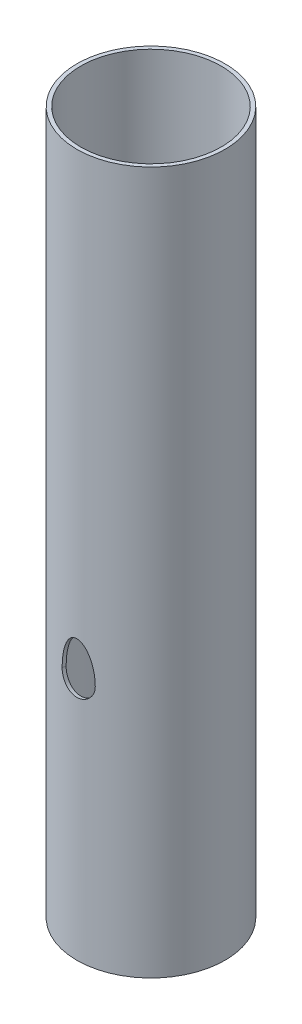
SolidWorks part; units mm, degrees
ref_plane "Front Plane" through (0, 0, 0) normal (0, 0, 1) x (1, 0, 0)
ref_plane "Top Plane" through (0, 0, 0) normal (0, 1, 0) x (1, 0, 0)
ref_plane "Right Plane" through (0, 0, 0) normal (1, 0, 0) x (0, 0, -1)
sketch "Sketch2" plane through (0, 0, 0) normal (0, 1, 0) x (1, 0, 0)
  circle A0 centre (0, 0) radius 36
  circle A1 centre (0, 0) radius 38
  dimension "D1" = 2
  dimension "D2" = 76
extrude "Boss-Extrude1" add sketch "Sketch2" along normal blind 360
ref_axis "Axis1" through (41.8, 0, 0) along (-1, 0, 0)
ref_plane "Plane1" through (0, 0, 0) normal (0, 0.2045, 0.9789) x (-1, 0, 0)
sketch "Sketch3" plane through (0, 0, 0) normal (0, 0.2045, 0.9789) x (-1, 0, 0)
  line L0 (0, 41.8) -> (0, -41.8) construction
  line L2 (-41.8, 0) -> (41.8, 0) construction
  arc A0 (8.5, -115) -> (-8.5, -115) centre (0, -115) ccw
  arc A1 (-8.5, -115) -> (8.5, -115) centre (0, -115) ccw construction
  ellipse E0 centre (0, -115) end of major axis (0, -132) minor radius 8.5 (-8.5, -115) -> (8.5, -115) ccw
  dimension "D1" = 17
  dimension "D2" = 115
  dimension "D3" = 17
extrude "Cut-Extrude1" cut sketch "Sketch3" along normal up to next
